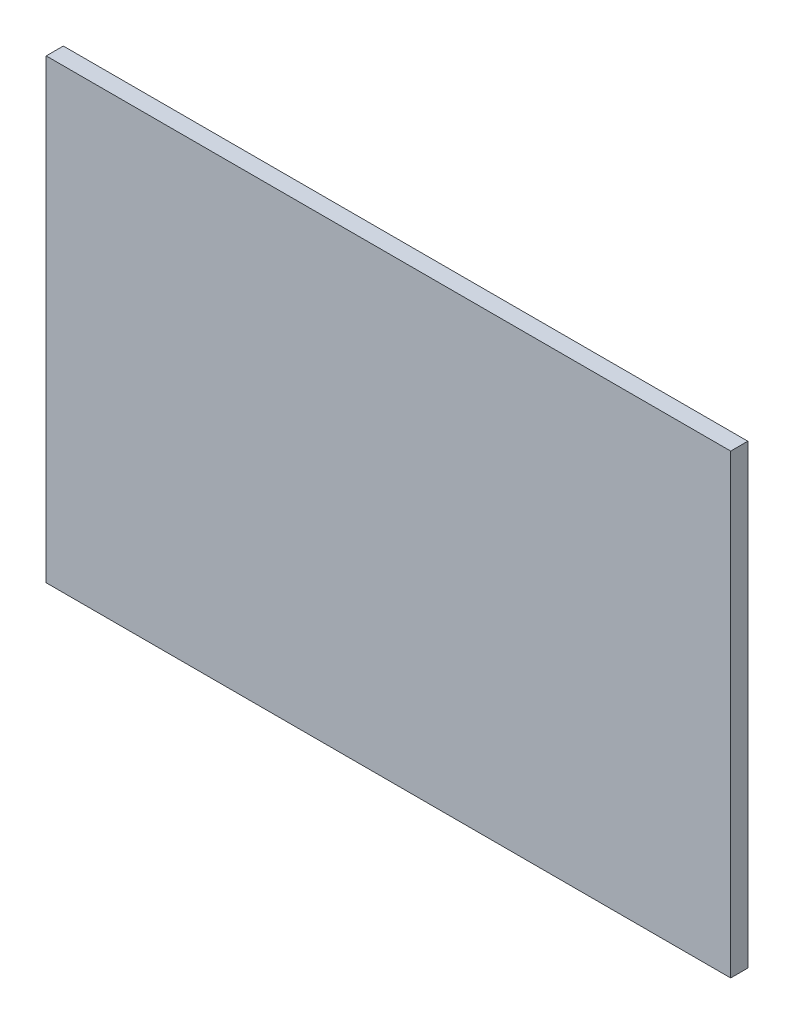
SolidWorks part; units mm, degrees
material "Лист 3,0 ГОСТ 19903-2015 / Ст3сп ГОСТ 14637-89"
ref_plane "Спереди" through (0, 0, 0) normal (0, 0, 1) x (1, 0, 0)
ref_plane "Сверху" through (0, 0, 0) normal (0, 1, 0) x (1, 0, 0)
ref_plane "Справа" through (0, 0, 0) normal (1, 0, 0) x (0, 0, -1)
sketch "Эскиз1" plane through (0, 0, 0) normal (0, 0, 1) x (1, 0, 0)
  line L1 (-60, -40) -> (60, -40)
  line L2 (-60, -40) -> (-60, 40)
  line L3 (-60, 40) -> (60, 40)
  line L4 (60, -40) -> (60, 40)
extrude "Бобышка-Вытянуть1" add sketch "Эскиз1" along normal blind 3
